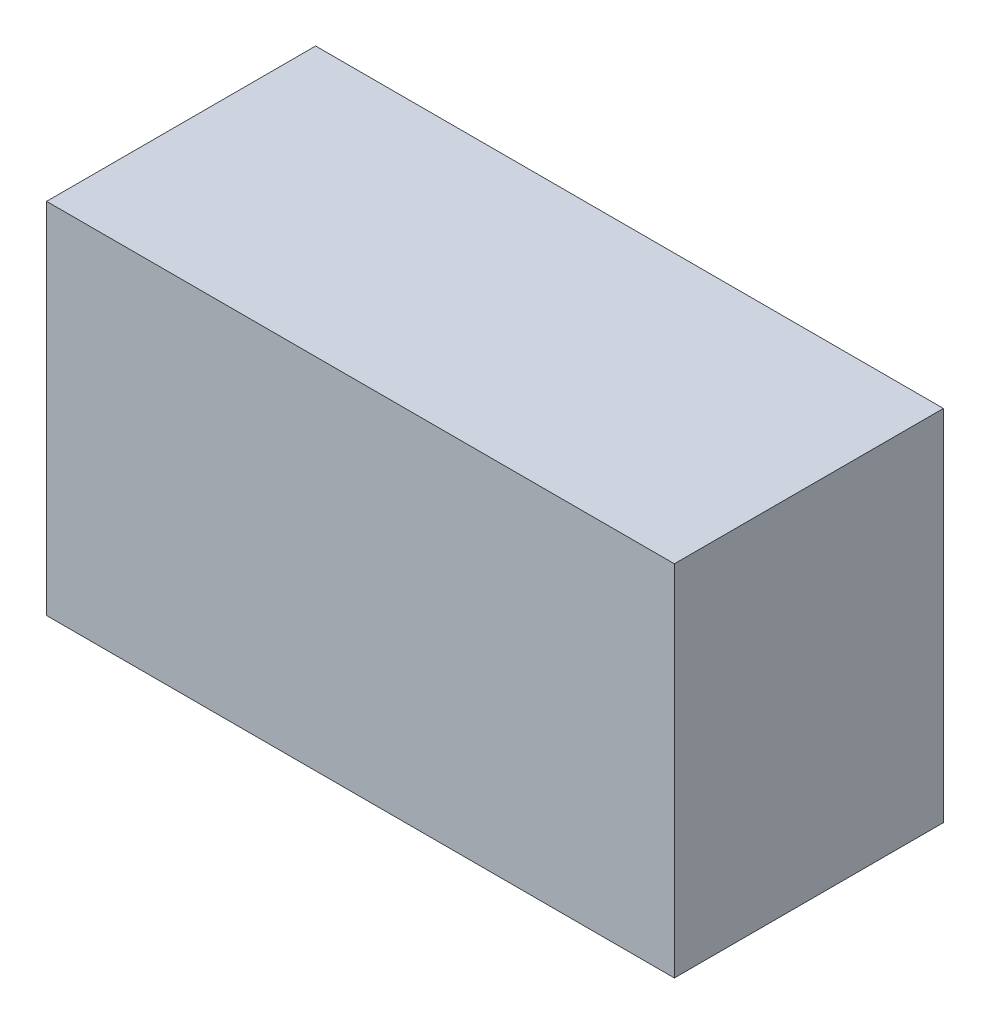
SolidWorks part; units mm, degrees
ref_plane "前视基准面" through (0, 0, 0) normal (0, 0, 1) x (1, 0, 0)
ref_plane "上视基准面" through (0, 0, 0) normal (0, 1, 0) x (1, 0, 0)
ref_plane "右视基准面" through (0, 0, 0) normal (1, 0, 0) x (0, 0, -1)
other "Configuration Table"
sketch "草图1" plane through (0, 0, 0) normal (0, 0, 1) x (1, 0, 0)
  line L1 (-35, -20) -> (35, -20)
  line L2 (-35, -20) -> (-35, 20)
  line L3 (-35, 20) -> (35, 20)
  line L4 (35, -20) -> (35, 20)
  line L5 (-35, -20) -> (35, 20) construction
  line L6 (-35, 20) -> (35, -20) construction
  point P0 (0, 0)
  dimension "D1" = 40
  dimension "D2" = 70
extrude "凸台-拉伸1" add sketch "草图1" along normal blind 30
